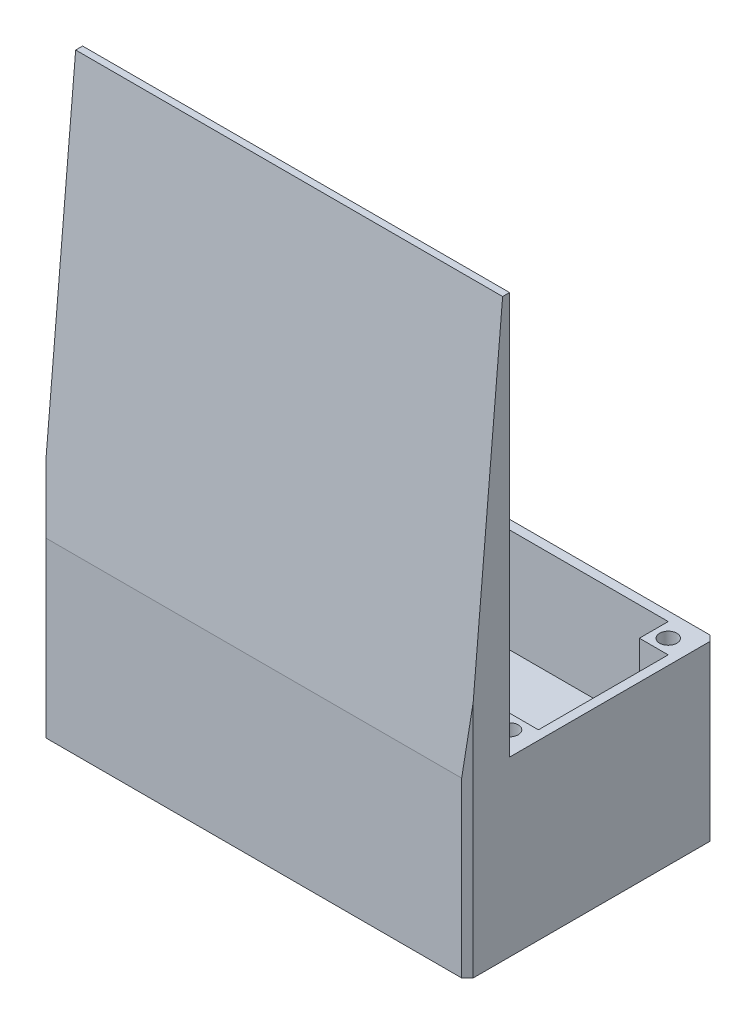
SolidWorks part; units mm, degrees
ref_plane "前视基准面" through (0, 0, 0) normal (0, 0, 1) x (1, 0, 0)
ref_plane "上视基准面" through (0, 0, 0) normal (0, 1, 0) x (1, 0, 0)
ref_plane "右视基准面" through (0, 0, 0) normal (1, 0, 0) x (0, 0, -1)
sketch "草图1" plane through (0, 0, 0) normal (0, 1, 0) x (1, 0, 0)
  line L1 (-37, 21.5) -> (37, 21.5)
  line L2 (-37, 21.5) -> (-37, -21.5)
  line L3 (-37, -21.5) -> (37, -21.5)
  line L4 (37, 21.5) -> (37, -21.5)
  line L5 (-37, 21.5) -> (37, -21.5) construction
  line L6 (-37, -21.5) -> (37, 21.5) construction
  point P0 (0, 0)
  dimension "D1" = 43
  dimension "D2" = 74
extrude "凸台-拉伸1" add sketch "草图1" along normal blind 30
sketch "草图7" plane through (-37, 0, 0) normal (-1, 0, 0) x (0, 0, 1)
  line L0 (21.5, 30) -> (15.3991, 99.7336)
  line L1 (-21.5, 30) -> (21.5, 30) construction
  line L3 (14.1991, 30) -> (21.5, 30)
  line L4 (15.3991, 99.7336) -> (14.1991, 99.7336)
  line L5 (14.1991, 99.7336) -> (14.1991, 30)
  dimension "D1" = 70
  dimension "D2" = 85
  dimension "D3" = 1.2
extrude "凸台-拉伸4" add sketch "草图7" against normal through all
ref_plane "基准面4" through (0, 1.99, 22.746) normal (0, 0.0872, 0.9962) x (1, 0, 0)
sketch "草图8" plane through (0, 1.99, 22.746) normal (0, 0.0872, 0.9962) x (1, 0, 0)
  line L0 (0, 98.012) -> (0, 28.012) construction
  line L3 (37, 98.012) -> (-37, 98.012) construction
  line L6 (-33.5, 96.512) -> (33.5, 96.512)
  line L7 (-33.5, 96.512) -> (-33.5, 29.512)
  line L8 (-33.5, 29.512) -> (33.5, 29.512)
  line L9 (33.5, 96.512) -> (33.5, 29.512)
  line L10 (-37, 28.012) -> (37, 28.012) construction
  point P14 (0, 53.05)
  dimension "D2" = 67
  dimension "D1" = 67
  dimension "D3" = 1.5
extrude "切除-拉伸2" cut sketch "草图8" against normal up to next
sketch "草图10" plane through (0, 30, 0) normal (0, 1, 0) x (1, 0, 0)
  line L4 (-35.4, -12.5991) -> (35.4, -12.5991)
  line L6 (-35.4, -12.5991) -> (35.4, -12.5991)
  line L18 (35.4, -12.5991) -> (35.4, 19.9)
  line L19 (35.4, 19.9) -> (-35.4, 19.9)
  line L22 (35.4, -12.5991) -> (35.4, 19.9)
  line L23 (35.4, 19.9) -> (-35.4, 19.9)
  line L41 (-35.4, 19.9) -> (-35.4, -12.5991)
  line L43 (-35.4, 19.9) -> (-35.4, -12.5991)
  dimension "D1" = 1.6
extrude "切除-拉伸3" cut sketch "草图10" against normal blind 18
sketch "草图11" plane through (0, 0, 14.1991) normal (0, 0, -1) x (-1, 0, 0)
  line L0 (-37, 30) -> (37, 30) construction
  line L2 (-33.5, 30) -> (33.5, 30)
  line L4 (33.5, 31.3897) -> (33.5, 30)
  line L5 (-33.5, 31.3897) -> (-33.5, 30)
  line L6 (33.5, 31.3897) -> (-33.5, 31.3897) construction
  line L7 (33.5, 31.3897) -> (-33.5, 31.3897)
extrude "切除-拉伸5" cut sketch "草图11" against normal up to surface (5.9747 mm away) up to face at (0, 64.7622, 17.2541)
sketch "草图12" plane through (0, 12, 0) normal (0, 1, 0) x (1, 0, 0)
  line L1 (-35.4, 19.9) -> (-30.4, 19.9)
  line L2 (-35.4, 19.9) -> (-35.4, 14.9)
  line L3 (-35.4, 14.9) -> (-30.4, 14.9)
  line L4 (-30.4, 19.9) -> (-30.4, 14.9)
  line L5 (35.4, 19.9) -> (30.4, 19.9)
  line L6 (35.4, 19.9) -> (35.4, 14.9)
  line L7 (35.4, 14.9) -> (30.4, 14.9)
  line L8 (30.4, 19.9) -> (30.4, 14.9)
  line L9 (-35.4, -12.5991) -> (-30.4, -12.5991)
  line L10 (-35.4, -12.5991) -> (-35.4, -7.5991)
  line L11 (-35.4, -7.5991) -> (-30.4, -7.5991)
  line L12 (-30.4, -12.5991) -> (-30.4, -7.5991)
  line L13 (35.4, -12.5991) -> (30.4, -12.5991)
  line L14 (35.4, -12.5991) -> (35.4, -7.5991)
  line L15 (35.4, -7.5991) -> (30.4, -7.5991)
  line L16 (30.4, -12.5991) -> (30.4, -7.5991)
  circle A0 centre (-32.9046, 17.5139) radius 1.5
  circle A2 centre (32.9, 17.4) radius 1.5
  circle A3 centre (-32.9, -10.0991) radius 1.5
  circle A4 centre (32.9, -10.0991) radius 1.5
  dimension "D9" = 2.5
  dimension "D10" = 2.5
  dimension "D11" = 2.5
  dimension "D12" = 2.5
  dimension "D1" = 5
  dimension "D2" = 5
  dimension "D3" = 5
  dimension "D4" = 5
  dimension "D5" = 5
  dimension "D6" = 5
  dimension "D7" = 5
  dimension "D8" = 5
extrude "凸台-拉伸6" add sketch "草图12" along normal up to surface (18 mm away) up to face at (0, 30, -3.6505)
chamfer "倒角1" distance 1 angle 45 4 edges at (-37, 15, 21.5) (37, 15, 21.5) (37, 15, -21.5) (-37, 15, -21.5)
